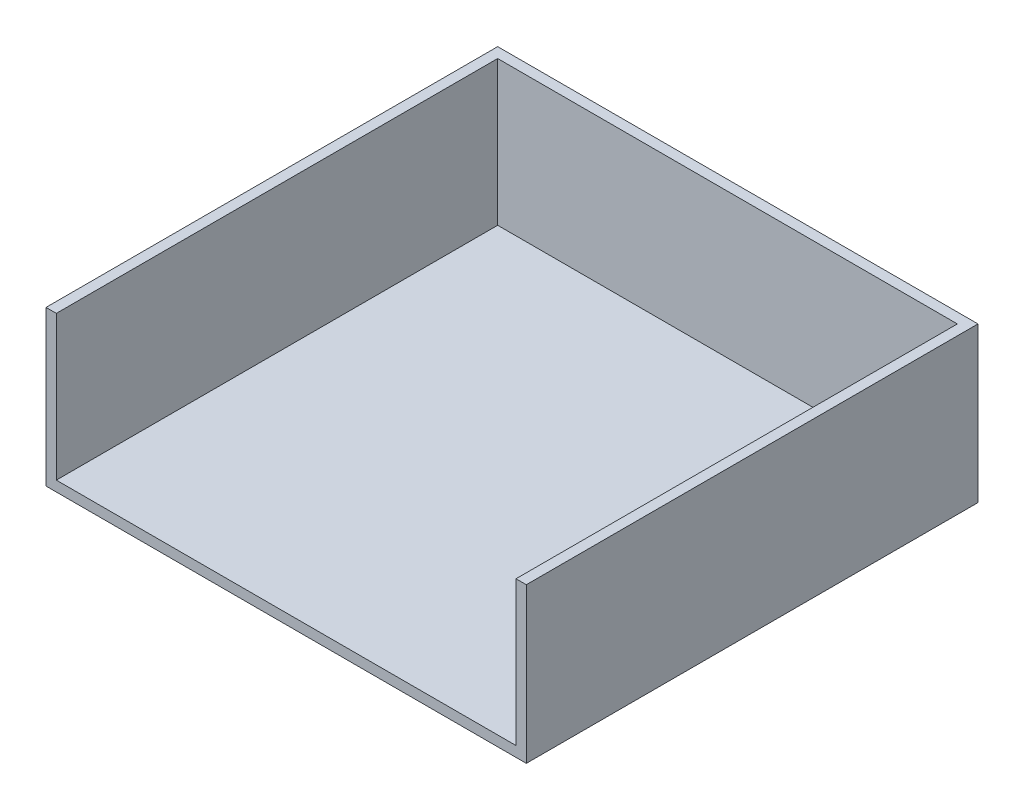
SolidWorks part; units mm, degrees
ref_plane "Front Plane" through (0, 0, 0) normal (0, 0, 1) x (1, 0, 0)
ref_plane "Top Plane" through (0, 0, 0) normal (0, 1, 0) x (1, 0, 0)
ref_plane "Right Plane" through (0, 0, 0) normal (1, 0, 0) x (0, 0, -1)
sketch "Sketch1" plane through (0, 0, 0) normal (0, 1, 0) x (1, 0, 0)
  line L1 (0, 0) -> (89.12, 0)
  line L2 (0, 0) -> (0, 85.57)
  line L3 (0, 85.57) -> (89.12, 85.57)
  line L4 (89.12, 0) -> (89.12, 85.57)
  dimension "D1" = 89.12
  dimension "D2" = 85.57
extrude "Boss-Extrude1" add sketch "Sketch1" along normal blind 2
sketch "Sketch3" plane through (0, 0, 0) normal (0, 0, 1) x (1, 0, 0)
  line L1 (0, 0) -> (-2, 0)
  line L2 (0, 0) -> (0, 30)
  line L3 (0, 30) -> (-2, 30)
  line L4 (-2, 0) -> (-2, 30)
  dimension "D1" = 2
  dimension "D2" = 30
extrude "Boss-Extrude2" add sketch "Sketch3" against normal blind 85.57
sketch "Sketch4" plane through (0, 0, 0) normal (0, 0, 1) x (1, 0, 0)
  line L1 (89.12, 0) -> (91.12, 0)
  line L2 (89.12, 0) -> (89.12, 30)
  line L3 (89.12, 30) -> (91.12, 30)
  line L4 (91.12, 0) -> (91.12, 30)
  dimension "D1" = 30
  dimension "D2" = 2
extrude "Boss-Extrude3" add sketch "Sketch4" against normal blind 85.57
sketch "Sketch5" plane through (0, 0, 0) normal (0, 1, 0) x (1, 0, 0)
  line L1 (-2, 85.57) -> (91.12, 85.57)
  line L2 (-2, 85.57) -> (-2, 87.57)
  line L3 (-2, 87.57) -> (91.12, 87.57)
  line L4 (91.12, 85.57) -> (91.12, 87.57)
  dimension "D1" = 2
extrude "Boss-Extrude4" add sketch "Sketch5" along normal blind 30
equation "\"tol1\"= 0.1cm"
equation "\"D1@Sketch1\"=8.812cm +\"tol1\""
equation "\"D2@Sketch1\"=8.457cm +\"tol1\""
equation "\"D1@Boss-Extrude2\"=8.457 +\"tol1\""
equation "\"D1@Boss-Extrude3\"=8.457 +\"tol1\""
